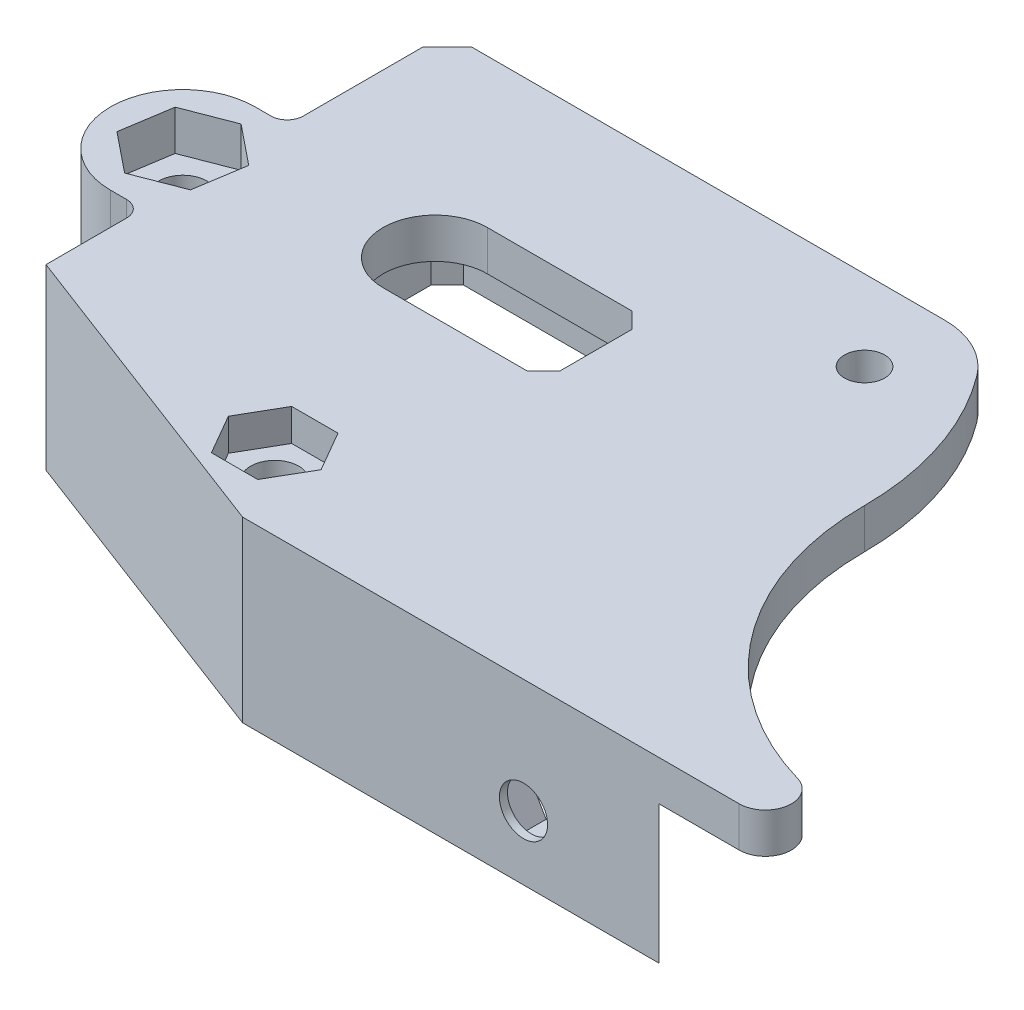
SolidWorks part; units mm, degrees
ref_plane "Front Plane" through (0, 0, 0) normal (0, 0, 1) x (1, 0, 0)
ref_plane "Top Plane" through (0, 0, 0) normal (0, 1, 0) x (1, 0, 0)
ref_plane "Right Plane" through (0, 0, 0) normal (1, 0, 0) x (0, 0, -1)
sketch "Sketch2" plane through (0, 0, 0) normal (0, 1, 0) x (1, 0, 0)
  line L0 (0, -40) -> (-72.5, -40) construction
  line L6 (-112, 25) -> (-112, -25)
  line L9 (-72.5, -40) -> (-20.6155, -40)
  line L10 (-102, 21) -> (-60, 21) construction
  line L11 (-102, 21) -> (-102, -21) construction
  line L12 (-102, -21) -> (-60, -21) construction
  line L13 (-60, 21) -> (-60, -21) construction
  line L14 (-102, 21) -> (-60, -21) construction
  line L21 (-102, -21) -> (-60, 21) construction
  line L22 (-29.4788, -34) -> (-77.0327, -34)
  line L23 (-108, -22.2403) -> (-108, 21)
  line L24 (-108, 21) -> (-60, 21)
  line L25 (-72.5, -40) -> (-112, -25)
  line L26 (-77.0327, -34) -> (-108, -22.2403)
  line L27 (-112, 25) -> (-56, 25)
  arc A2 (-22.016, 33.3961) -> (0, -40) centre (0, 0) cw construction
  arc A3 (-22.016, 33.3961) -> (-60, 21) centre (-63.6326, 96.5245) cw construction
  circle A8 centre (0, 0) radius 40 construction
  arc A9 (-20.6155, -40) -> (-29.4788, -34) centre (0, 0) cw
  circle A10 centre (-50, 15) radius 11 construction
  arc A11 (-60, 21) -> (-56, 25) centre (-50, 15) cw
  point P9 (-81, 0)
  point P20 (-112, 0)
  dimension "D1" = 40
  dimension "D2" = 72.5
  dimension "D6" = 45
  dimension "D11" = 15
  dimension "D14" = 4
  dimension "D9" = 22
  dimension "D3" = 42
  dimension "D4" = 42
  dimension "D5" = 81
  dimension "D7" = 6
  dimension "D8" = 4
  dimension "D10" = 50
  dimension "D12" = 4
  dimension "D13" = 50
  dimension "D15" = 52
extrude "Boss-Extrude1" add sketch "Sketch2" along normal blind 17.2
chamfer "Chamfer1" distance 3 angle 45 1 edges at (-112, 8.6, -25)
chamfer "Chamfer2" distance 2 angle 45 1 edges at (-108, 8.6, -21)
sketch "Sketch3" plane through (0, 17.2, 0) normal (0, 1, 0) x (1, 0, 0)
  line L0 (-88.5, 6.5) -> (-68.5, 6.5)
  line L1 (-72.5, -40) -> (-20.6155, -40)
  line L2 (-20.6155, -40) -> (-10.6155, -40)
  line L3 (-68.5, -6.5) -> (-88.5, -6.5)
  line L4 (-50, 25) -> (-109, 25)
  line L5 (-112, 22) -> (-112, -25)
  line L6 (-72.5, -40) -> (0, -40) construction
  line L7 (-112, -25) -> (-72.5, -40)
  line L8 (-109, 25) -> (-112, 22)
  line L9 (-68.5, 6.5) -> (-68.5, -6.5)
  circle A0 centre (-50, 15) radius 2.5
  arc A1 (0, -40) -> (-23.5728, 32.316) centre (0, 0) ccw construction
  arc A2 (-88.5, 6.5) -> (-88.5, -6.5) centre (-88.5, 0) ccw
  circle A3 centre (-78.5, -30) radius 3
  arc A4 (-35, 0) -> (-9.7132, -33.6252) centre (0, 0) ccw
  arc A5 (-35, 0) -> (-42, 21) centre (-70, 0) ccw
  arc A6 (-42, 21) -> (-50, 25) centre (-50, 15) ccw
  arc A7 (-10.6155, -40) -> (-9.7132, -33.6252) centre (-10.6155, -36.7487) ccw
  dimension "D1" = 5
  dimension "D2" = 40
  dimension "D3" = 35
  dimension "D5" = 6
  dimension "D8" = 6.5
  dimension "D7" = 88.5
  dimension "D4" = 10
  dimension "D6" = 30
  dimension "D9" = 20
  dimension "D10" = 78.5
extrude "Boss-Extrude2" add sketch "Sketch3" along normal blind 5
ref_axis "Axis1" through (0, 73.1015, 0) along (0, -1, 0)
sketch "Sketch5" plane through (0, 17.2, 0) normal (0, -1, 0) x (1, 0, 0)
  line L0 (-73.5, 30) -> (-73.5, 34)
  line L1 (-29.4788, 34) -> (-77.0327, 34) construction
  line L2 (-83.5, 30) -> (-83.5, 34)
  line L3 (-83.5, 34) -> (-73.5, 34)
  arc A1 (-83.5, 30) -> (-73.5, 30) centre (-78.5, 30) ccw
  circle A2 centre (-78.5, 30) radius 3
  dimension "D1" = 6
extrude "Boss-Extrude3" add sketch "Sketch5" along normal up to surface (17.2 mm away) up to face at (-80.921, 0, 5.1882)
sketch "Sketch7" plane through (0, 22.2, 0) normal (0, 1, 0) x (1, 0, 0)
  line L0 (-50, 25) -> (-109, 25) construction
  line L1 (-112, 22) -> (-112, -25) construction
  line L2 (-112, 5.05) -> (-112, -12.95)
  line L3 (-112, -12.95) -> (-116, -12.95)
  line L4 (-112, 5.05) -> (-116, 5.05)
  arc A0 (-116, 5.05) -> (-116, -12.95) centre (-116, -3.95) ccw
  dimension "D1" = 18
  dimension "D2" = 4
  dimension "D3" = 28.95
extrude "Boss-Extrude4" add sketch "Sketch7" against normal up to surface (22.2 mm away) up to face at (-80.5346, 0, 9.9202)
fillet "Fillet1" radius 2 2 edges at (-112, 11.1, 12.95) (-112, 11.1, -5.05)
sketch "Sketch8" plane through (0, 22.2, 0) normal (0, 1, 0) x (1, 0, 0)
  circle A0 centre (-116, -3.95) radius 3
  dimension "D1" = 6
extrude "Cut-Extrude3" cut sketch "Sketch8" against normal blind 31 contours A0
sketch "Sketch9" plane through (0, 22.2, 0) normal (0, 1, 0) x (1, 0, 0)
  line L1 (-110.0748, -1.6642) -> (-115.0169, 2.3243)
  line L2 (-115.0169, 2.3243) -> (-120.9422, 0.0385)
  line L3 (-120.9422, 0.0385) -> (-121.9252, -6.2358)
  line L4 (-121.9252, -6.2358) -> (-116.9831, -10.2243)
  line L5 (-116.9831, -10.2243) -> (-111.0578, -7.9385)
  line L6 (-111.0578, -7.9385) -> (-110.0748, -1.6642)
  circle A0 centre (-116, -3.95) radius 5.5 construction
  dimension "D1" = 11
extrude "Cut-Extrude4" cut sketch "Sketch9" against normal blind 5
sketch "Sketch10" plane through (0, 0, 40) normal (0, 0, 1) x (1, 0, 0)
  line L0 (-72.5, 0) -> (-20.6155, 0) construction
  circle A0 centre (-37.5, 8) radius 3
  dimension "D2" = 6
  dimension "D3" = 8
  dimension "D1" = 37.5
extrude "Cut-Extrude5" cut sketch "Sketch10" against normal blind 44 contours A0
fillet "Fillet2" radius 2 2 edges at (-83.5, 8.6, 31.5441) (-73.5, 8.6, 34)
chamfer "Chamfer3" distance 2 angle 45 2 edges at (-68.5, 19.7, -6.5) (-68.5, 19.7, 6.5)
sketch "Sketch11" plane through (0, 22.2, 0) normal (0, 1, 0) x (1, 0, 0)
  line L1 (-72.7265, -30) -> (-75.6132, -25)
  line L2 (-75.6132, -25) -> (-81.3868, -25)
  line L3 (-81.3868, -25) -> (-84.2735, -30)
  line L4 (-84.2735, -30) -> (-81.3868, -35)
  line L5 (-81.3868, -35) -> (-75.6132, -35)
  line L6 (-75.6132, -35) -> (-72.7265, -30)
  circle A0 centre (-78.5, -30) radius 5 construction
  dimension "D1" = 10
extrude "Cut-Extrude6" cut sketch "Sketch11" against normal blind 4
sketch "Sketch12" plane through (0, 0, 34) normal (0, 0, -1) x (-1, 0, 0)
  line L1 (43.8509, 8) -> (40.6754, 13.5)
  line L2 (40.6754, 13.5) -> (34.3246, 13.5)
  line L3 (34.3246, 13.5) -> (31.1491, 8)
  line L4 (31.1491, 8) -> (34.3246, 2.5)
  line L5 (34.3246, 2.5) -> (40.6754, 2.5)
  line L6 (40.6754, 2.5) -> (43.8509, 8)
  circle A0 centre (37.5, 8) radius 5.5 construction
  dimension "D1" = 11
extrude "Cut-Extrude7" cut sketch "Sketch12" against normal blind 5
sketch "Sketch13" plane through (0, 17.2, 0) normal (0, -1, 0) x (1, 0, 0)
  circle A0 centre (-50, -15) radius 5.005
  dimension "D1" = 10.01
extrude "Cut-Extrude8" cut sketch "Sketch13" against normal blind 1
